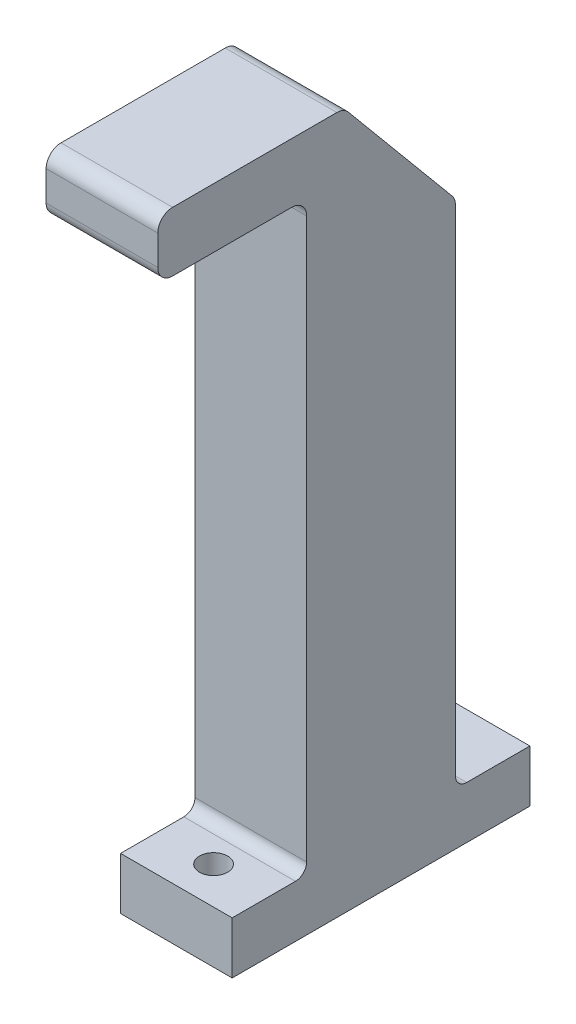
SolidWorks part; units mm, degrees
ref_plane "Front Plane" through (0, 0, 0) normal (0, 0, 1) x (1, 0, 0)
ref_plane "Top Plane" through (0, 0, 0) normal (0, 1, 0) x (1, 0, 0)
ref_plane "Right Plane" through (0, 0, 0) normal (1, 0, 0) x (0, 0, -1)
sketch "Sketch1" plane through (0, 0, 0) normal (1, 0, 0) x (0, 0, -1)
  line L0 (0, 0) -> (0, 8)
  line L1 (0, 8) -> (25, 8)
  line L4 (40, -10) -> (40, -85.68)
  line L5 (40, -85.68) -> (20, -85.68)
  line L6 (20, -85.68) -> (20, 0)
  line L7 (20, 0) -> (0, 0)
  line L8 (25, 8) -> (40, -10)
  dimension "D1" = 85.68
  dimension "D2" = 8
  dimension "D3" = 20
  dimension "D4" = 25
  dimension "D5" = 20
  dimension "D6" = 75.68
extrude "Boss-Extrude1" add sketch "Sketch1" along normal mid plane 15
sketch "Sketch2" plane through (0, 8, 0) normal (0, 1, 0) x (1, 0, 0)
  line L0 (-7.5, 40) -> (-7.5, 25) construction
  line L1 (7.5, 40) -> (7.5, 25) construction
  line L2 (7.5, 25) -> (-7.5, 25) construction
  circle A0 centre (-4, 31) radius 2
  circle A1 centre (4, 31) radius 2
  dimension "D1" = 4
  dimension "D2" = 4
  dimension "D6" = 6
  dimension "D3" = 3.5
  dimension "D4" = 3.5
  dimension "D5" = 6
sketch "Sketch3" plane through (0, 8, 0) normal (0, 1, 0) x (1, 0, 0)
  circle A0 centre (-4, 31) radius 1.05
  circle A1 centre (4, 31) radius 1.05
  dimension "D1" = 2.1
  dimension "D2" = 2.1
fillet "Fillet1" radius 2 5 edges at (0, -10, -40) (0, 8, -25) (0, 8, 0) (0, 0, 0) (0, 0, -20)
sketch "Sketch4" plane through (0, -85.68, 0) normal (0, -1, 0) x (1, 0, 0)
  line L0 (7.5, -40) -> (-7.5, -40)
  line L1 (7.5, -40) -> (7.5, -50)
  line L2 (-7.5, -40) -> (-7.5, -50)
  line L3 (7.5, -50) -> (-7.5, -50)
  line L4 (7.5, -20) -> (-7.5, -20)
  line L5 (7.5, -20) -> (7.5, -10)
  line L6 (-7.5, -20) -> (-7.5, -10)
  line L7 (7.5, -10) -> (-7.5, -10)
  circle A0 centre (0, -45) radius 1.6
  circle A1 centre (0, -15) radius 1.8908
  dimension "D3" = 3.2
  dimension "D4" = 3.7816
  dimension "D5" = 5
  dimension "D6" = 5
  dimension "D1" = 10
  dimension "D2" = 10
extrude "Boss-Extrude2" add sketch "Sketch4" against normal blind 7
fillet "Fillet2" radius 1.5 2 edges at (0, -78.68, -20) (0, -78.68, -40)
